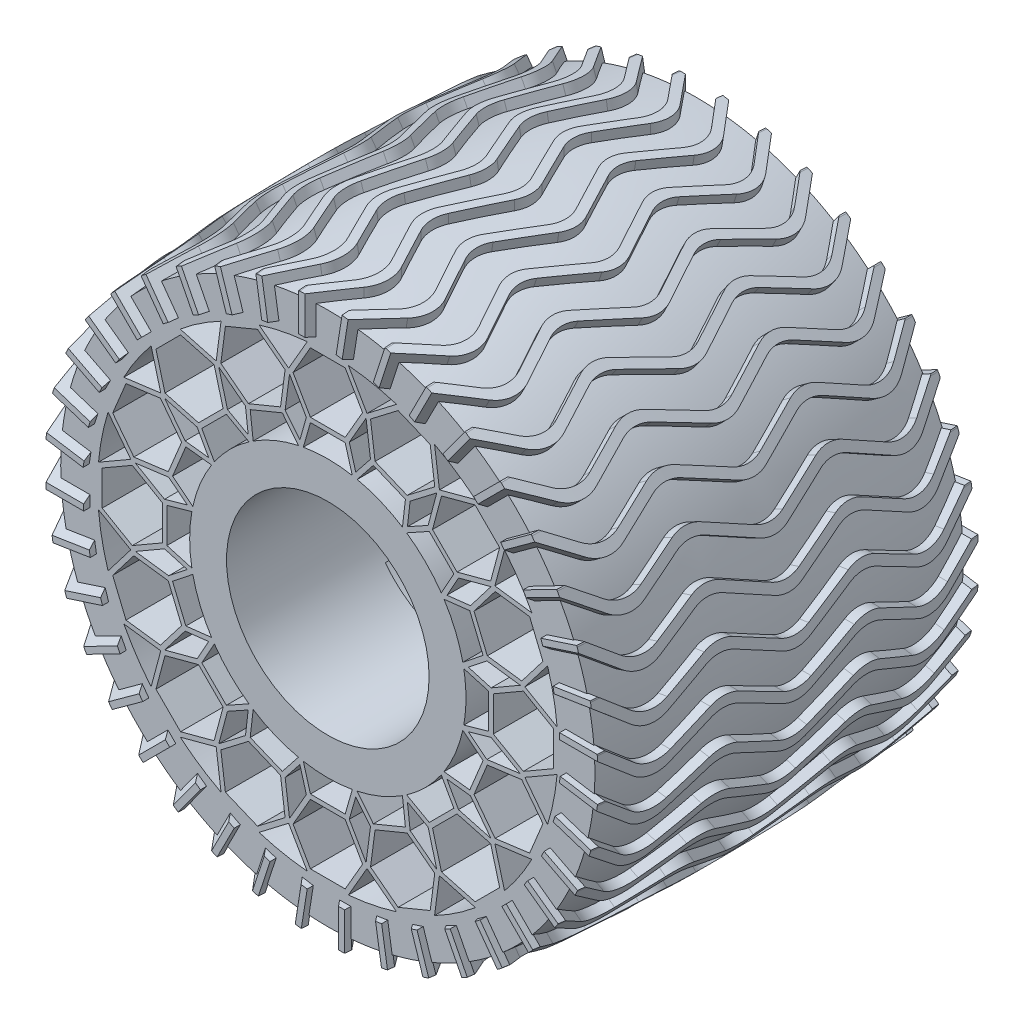
SolidWorks part; units mm, degrees
ref_plane "Alzado" through (0, 0, 0) normal (0, 0, 1) x (1, 0, 0)
ref_plane "Planta" through (0, 0, 0) normal (0, 1, 0) x (1, 0, 0)
ref_plane "Vista lateral" through (0, 0, 0) normal (1, 0, 0) x (0, 0, -1)
sketch "Croquis3" plane through (0, 0, 0) normal (1, 0, 0) x (0, 0, -1)
  line L0 (-55, 0) -> (55, 0) construction
  point P4 (0, 0)
  dimension "D1" = 110
sketch "Croquis2" plane through (0, 0, 0) normal (1, 0, 0) x (0, 0, -1)
  line L0 (0, 0) -> (0, 75) construction
  line L1 (-60, 75) -> (60, 75)
  line L2 (0, 75) -> (0, 87) construction
  line L3 (0, 87) -> (0, 90) construction
  line L4 (-60, 87) -> (60, 87) construction
  line L5 (-60, 87) -> (-60, 75)
  line L6 (60, 87) -> (60, 75)
  line L7 (-60, 33) -> (-15, 33)
  line L8 (60.1117, 33) -> (60.1117, 45)
  line L9 (60.1117, 45) -> (-60, 45)
  line L10 (-60, 45) -> (-60, 33)
  line L11 (-50, 40) -> (50, 40)
  line L14 (15, 33) -> (60.1117, 33)
  line L15 (-15, 33) -> (-15, 35)
  line L16 (-15, 35) -> (-50, 35)
  line L17 (-50, 35) -> (-50, 40)
  line L18 (15, 33) -> (15, 35)
  line L19 (15, 35) -> (50, 35)
  line L20 (50, 35) -> (50, 40)
  arc A0 (60, 87) -> (-60, 87) centre (0, -511.5) ccw
  point P6 (0, 75)
  point P11 (0, 87)
  point P15 (0, 33)
  point P18 (0.0558, 45)
  point P20 (0, 40)
  dimension "D1" = 75
  dimension "D2" = 120
  dimension "D3" = 12
  dimension "D4" = 3
  dimension "D5" = 12
  dimension "D6" = 33
  dimension "D7" = 100
  dimension "D8" = 2
  dimension "D9" = 5
  dimension "D10" = 30
  dimension "D11" = 30
revolve "Revolución1" add sketch "Croquis2" angle 360 about L0
sketch "Croquis4" plane through (0, 0, 0) normal (0, 0, 1) x (1, 0, 0)
  line L0 (-66.7936, 34.7304) -> (-71.7883, 22.6722)
  line L1 (71.7883, 22.6722) -> (66.7936, 34.7304)
  line L2 (57.6475, 48.4185) -> (48.4185, 57.6475)
  line L3 (34.7304, 66.7936) -> (22.6722, 71.7883)
  line L4 (6.5259, 75) -> (-6.5259, 75)
  line L5 (-22.6722, 71.7883) -> (-34.7304, 66.7936)
  line L6 (-48.4185, 57.6475) -> (-57.6475, 48.4185)
  line L7 (-75, 6.5259) -> (-75, -6.5259)
  line L8 (-71.7883, -22.6722) -> (-66.7936, -34.7304)
  line L9 (-57.6475, -48.4185) -> (-48.4185, -57.6475)
  line L10 (-34.7304, -66.7936) -> (-22.6722, -71.7883)
  line L11 (-6.5259, -75) -> (6.5259, -75)
  line L12 (22.6722, -71.7883) -> (34.7304, -66.7936)
  line L13 (48.4185, -57.6475) -> (57.6475, -48.4185)
  line L14 (66.7936, -34.7304) -> (71.7883, -22.6722)
  line L15 (75, -6.5259) -> (75, 6.5259)
  line L16 (0, 0) -> (75, 0) construction
  line L17 (14.9184, 75) -> (-14.9184, -75) construction
  line L18 (-14.9184, 75) -> (14.9184, -75) construction
  line L19 (0, 0) -> (0, 75) construction
  line L20 (-6.5259, 75) -> (-12.7679, 64.1885)
  line L31 (-12.4695, 62.6885) -> (-6.9901, 53.1979)
  line L32 (-6.9901, 53.1979) -> (-9.1077, 45.7875)
  line L33 (-7.9763, 44.2875) -> (-5.6598, 52.3938)
  line L34 (11.3197, 63.6969) -> (5.6598, 73.5)
  line L35 (5.6598, 73.5) -> (-5.6598, 73.5)
  line L36 (-5.6598, 73.5) -> (-11.3197, 63.6969)
  line L37 (-11.3197, 63.6969) -> (-5.6598, 53.8938)
  line L38 (-5.6598, 53.8938) -> (5.6598, 53.8938)
  line L39 (5.6598, 53.8938) -> (11.3197, 63.6969)
  line L40 (-5.6598, 52.3938) -> (5.6598, 52.3938)
  line L41 (5.6598, 52.3938) -> (7.9763, 44.2875)
  line L42 (34.8337, 54.5164) -> (33.3562, 65.7392)
  line L43 (33.3562, 65.7392) -> (22.8982, 70.0711)
  line L44 (22.8982, 70.0711) -> (13.9177, 63.1801)
  line L45 (13.9177, 63.1801) -> (15.3953, 51.9573)
  line L46 (15.3953, 51.9573) -> (25.8533, 47.6254)
  line L47 (6.9901, 53.1979) -> (9.1077, 45.7875)
  line L48 (25.8533, 47.6254) -> (34.8337, 54.5164)
  line L49 (12.4695, 62.6885) -> (6.9901, 53.1979)
  line L50 (6.5259, 75) -> (12.7679, 64.1885)
  line L51 (22.6722, 71.7883) -> (12.7679, 64.1885)
  line L52 (12.4695, 62.6885) -> (13.8999, 51.8234)
  line L53 (9.5789, 43.9687) -> (14.8212, 50.5715)
  line L54 (13.8999, 51.8234) -> (9.1077, 45.7875)
  line L55 (25.2792, 46.2396) -> (24.3172, 37.8639)
  line L56 (26.8159, 46.4734) -> (25.9365, 38.8167)
  line L57 (14.8212, 50.5715) -> (25.2792, 46.2396)
  line L58 (35.5102, 53.1447) -> (26.8159, 46.4734)
  line L59 (34.7304, 66.7936) -> (36.3599, 54.4164)
  line L60 (53.0447, 37.0363) -> (55.9745, 47.9702)
  line L61 (55.9745, 47.9702) -> (47.9702, 55.9745)
  line L62 (47.9702, 55.9745) -> (37.0363, 53.0447)
  line L63 (37.0363, 53.0447) -> (34.1065, 42.1108)
  line L64 (34.1065, 42.1108) -> (42.1108, 34.1065)
  line L65 (42.1108, 34.1065) -> (53.0447, 37.0363)
  line L66 (48.4185, 57.6475) -> (36.3599, 54.4164)
  line L67 (35.5102, 53.1447) -> (32.6738, 42.5593)
  line L68 (25.6759, 36.956) -> (33.0459, 41.0501)
  line L69 (32.6738, 42.5593) -> (25.9365, 38.8167)
  line L70 (41.0501, 33.0459) -> (36.956, 25.6759)
  line L71 (42.5593, 32.6738) -> (38.8167, 25.9365)
  line L72 (33.0459, 41.0501) -> (41.0501, 33.0459)
  line L73 (53.1447, 35.5102) -> (42.5593, 32.6738)
  line L74 (57.6475, 48.4185) -> (54.4164, 36.3599)
  line L75 (63.1801, 13.9177) -> (70.0711, 22.8982)
  line L76 (70.0711, 22.8982) -> (65.7392, 33.3562)
  line L77 (65.7392, 33.3562) -> (54.5164, 34.8337)
  line L78 (54.5164, 34.8337) -> (47.6254, 25.8533)
  line L79 (47.6254, 25.8533) -> (51.9573, 15.3953)
  line L80 (51.9573, 15.3953) -> (63.1801, 13.9177)
  line L81 (66.7936, 34.7304) -> (54.4164, 36.3599)
  line L82 (53.1447, 35.5102) -> (46.4734, 26.8159)
  line L83 (37.8639, 24.3172) -> (46.2396, 25.2792)
  line L84 (46.4734, 26.8159) -> (38.8167, 25.9365)
  line L85 (50.5715, 14.8212) -> (43.9687, 9.5789)
  line L86 (51.8234, 13.8999) -> (45.7875, 9.1077)
  line L87 (46.2396, 25.2792) -> (50.5715, 14.8212)
  line L88 (62.6885, 12.4695) -> (51.8234, 13.8999)
  line L89 (71.7883, 22.6722) -> (64.1885, 12.7679)
  line L90 (63.6969, -11.3197) -> (73.5, -5.6598)
  line L91 (73.5, -5.6598) -> (73.5, 5.6598)
  line L92 (73.5, 5.6598) -> (63.6969, 11.3197)
  line L93 (63.6969, 11.3197) -> (53.8938, 5.6598)
  line L94 (53.8938, 5.6598) -> (53.8938, -5.6598)
  line L95 (53.8938, -5.6598) -> (63.6969, -11.3197)
  line L96 (75, 6.5259) -> (64.1885, 12.7679)
  line L97 (62.6885, 12.4695) -> (53.1979, 6.9901)
  line L98 (44.2875, 7.9763) -> (52.3938, 5.6598)
  line L99 (53.1979, 6.9901) -> (45.7875, 9.1077)
  line L100 (52.3938, -5.6598) -> (44.2875, -7.9763)
  line L101 (53.1979, -6.9901) -> (45.7875, -9.1077)
  line L102 (52.3938, 5.6598) -> (52.3938, -5.6598)
  line L103 (62.6885, -12.4695) -> (53.1979, -6.9901)
  line L104 (75, -6.5259) -> (64.1885, -12.7679)
  line L105 (54.5164, -34.8337) -> (65.7392, -33.3562)
  line L106 (65.7392, -33.3562) -> (70.0711, -22.8982)
  line L107 (70.0711, -22.8982) -> (63.1801, -13.9177)
  line L108 (63.1801, -13.9177) -> (51.9573, -15.3953)
  line L109 (51.9573, -15.3953) -> (47.6254, -25.8533)
  line L110 (47.6254, -25.8533) -> (54.5164, -34.8337)
  line L111 (71.7883, -22.6722) -> (64.1885, -12.7679)
  line L112 (62.6885, -12.4695) -> (51.8234, -13.8999)
  line L113 (43.9687, -9.5789) -> (50.5715, -14.8212)
  line L114 (51.8234, -13.8999) -> (45.7875, -9.1077)
  line L115 (46.2396, -25.2792) -> (37.8639, -24.3172)
  line L116 (46.4734, -26.8159) -> (38.8167, -25.9365)
  line L117 (50.5715, -14.8212) -> (46.2396, -25.2792)
  line L118 (53.1447, -35.5102) -> (46.4734, -26.8159)
  line L119 (66.7936, -34.7304) -> (54.4164, -36.3599)
  line L120 (37.0363, -53.0447) -> (47.9702, -55.9745)
  line L121 (47.9702, -55.9745) -> (55.9745, -47.9702)
  line L122 (55.9745, -47.9702) -> (53.0447, -37.0363)
  line L123 (53.0447, -37.0363) -> (42.1108, -34.1065)
  line L124 (42.1108, -34.1065) -> (34.1065, -42.1108)
  line L125 (34.1065, -42.1108) -> (37.0363, -53.0447)
  line L126 (57.6475, -48.4185) -> (54.4164, -36.3599)
  line L127 (53.1447, -35.5102) -> (42.5593, -32.6738)
  line L128 (36.956, -25.6759) -> (41.0501, -33.0459)
  line L129 (42.5593, -32.6738) -> (38.8167, -25.9365)
  line L130 (33.0459, -41.0501) -> (25.6759, -36.956)
  line L131 (32.6738, -42.5593) -> (25.9365, -38.8167)
  line L132 (41.0501, -33.0459) -> (33.0459, -41.0501)
  line L133 (35.5102, -53.1447) -> (32.6738, -42.5593)
  line L134 (48.4185, -57.6475) -> (36.3599, -54.4164)
  line L135 (13.9177, -63.1801) -> (22.8982, -70.0711)
  line L136 (22.8982, -70.0711) -> (33.3562, -65.7392)
  line L137 (33.3562, -65.7392) -> (34.8337, -54.5164)
  line L138 (34.8337, -54.5164) -> (25.8533, -47.6254)
  line L139 (25.8533, -47.6254) -> (15.3953, -51.9573)
  line L140 (15.3953, -51.9573) -> (13.9177, -63.1801)
  line L141 (34.7304, -66.7936) -> (36.3599, -54.4164)
  line L142 (35.5102, -53.1447) -> (26.8159, -46.4734)
  line L143 (24.3172, -37.8639) -> (25.2792, -46.2396)
  line L144 (26.8159, -46.4734) -> (25.9365, -38.8167)
  line L145 (14.8212, -50.5715) -> (9.5789, -43.9687)
  line L146 (13.8999, -51.8234) -> (9.1077, -45.7875)
  line L147 (25.2792, -46.2396) -> (14.8212, -50.5715)
  line L148 (12.4695, -62.6885) -> (13.8999, -51.8234)
  line L149 (22.6722, -71.7883) -> (12.7679, -64.1885)
  line L150 (-11.3197, -63.6969) -> (-5.6598, -73.5)
  line L151 (-5.6598, -73.5) -> (5.6598, -73.5)
  line L152 (5.6598, -73.5) -> (11.3197, -63.6969)
  line L153 (11.3197, -63.6969) -> (5.6598, -53.8938)
  line L154 (5.6598, -53.8938) -> (-5.6598, -53.8938)
  line L155 (-5.6598, -53.8938) -> (-11.3197, -63.6969)
  line L156 (6.5259, -75) -> (12.7679, -64.1885)
  line L157 (12.4695, -62.6885) -> (6.9901, -53.1979)
  line L158 (7.9763, -44.2875) -> (5.6598, -52.3938)
  line L159 (6.9901, -53.1979) -> (9.1077, -45.7875)
  line L160 (-5.6598, -52.3938) -> (-7.9763, -44.2875)
  line L161 (-6.9901, -53.1979) -> (-9.1077, -45.7875)
  line L162 (5.6598, -52.3938) -> (-5.6598, -52.3938)
  line L163 (-12.4695, -62.6885) -> (-6.9901, -53.1979)
  line L164 (-6.5259, -75) -> (-12.7679, -64.1885)
  line L165 (-34.8337, -54.5164) -> (-33.3562, -65.7392)
  line L166 (-33.3562, -65.7392) -> (-22.8982, -70.0711)
  line L167 (-22.8982, -70.0711) -> (-13.9177, -63.1801)
  line L168 (-13.9177, -63.1801) -> (-15.3953, -51.9573)
  line L169 (-15.3953, -51.9573) -> (-25.8533, -47.6254)
  line L170 (-25.8533, -47.6254) -> (-34.8337, -54.5164)
  line L171 (-22.6722, -71.7883) -> (-12.7679, -64.1885)
  line L172 (-12.4695, -62.6885) -> (-13.8999, -51.8234)
  line L173 (-9.5789, -43.9687) -> (-14.8212, -50.5715)
  line L174 (-13.8999, -51.8234) -> (-9.1077, -45.7875)
  line L175 (-25.2792, -46.2396) -> (-24.3172, -37.8639)
  line L176 (-26.8159, -46.4734) -> (-25.9365, -38.8167)
  line L177 (-14.8212, -50.5715) -> (-25.2792, -46.2396)
  line L178 (-35.5102, -53.1447) -> (-26.8159, -46.4734)
  line L179 (-34.7304, -66.7936) -> (-36.3599, -54.4164)
  line L180 (-53.0447, -37.0363) -> (-55.9745, -47.9702)
  line L181 (-55.9745, -47.9702) -> (-47.9702, -55.9745)
  line L182 (-47.9702, -55.9745) -> (-37.0363, -53.0447)
  line L183 (-37.0363, -53.0447) -> (-34.1065, -42.1108)
  line L184 (-34.1065, -42.1108) -> (-42.1108, -34.1065)
  line L185 (-42.1108, -34.1065) -> (-53.0447, -37.0363)
  line L186 (-48.4185, -57.6475) -> (-36.3599, -54.4164)
  line L187 (-35.5102, -53.1447) -> (-32.6738, -42.5593)
  line L188 (-25.6759, -36.956) -> (-33.0459, -41.0501)
  line L189 (-32.6738, -42.5593) -> (-25.9365, -38.8167)
  line L190 (-41.0501, -33.0459) -> (-36.956, -25.6759)
  line L191 (-42.5593, -32.6738) -> (-38.8167, -25.9365)
  line L192 (-33.0459, -41.0501) -> (-41.0501, -33.0459)
  line L193 (-53.1447, -35.5102) -> (-42.5593, -32.6738)
  line L194 (-57.6475, -48.4185) -> (-54.4164, -36.3599)
  line L195 (-63.1801, -13.9177) -> (-70.0711, -22.8982)
  line L196 (-70.0711, -22.8982) -> (-65.7392, -33.3562)
  line L197 (-65.7392, -33.3562) -> (-54.5164, -34.8337)
  line L198 (-54.5164, -34.8337) -> (-47.6254, -25.8533)
  line L199 (-47.6254, -25.8533) -> (-51.9573, -15.3953)
  line L200 (-51.9573, -15.3953) -> (-63.1801, -13.9177)
  line L201 (-66.7936, -34.7304) -> (-54.4164, -36.3599)
  line L202 (-53.1447, -35.5102) -> (-46.4734, -26.8159)
  line L203 (-37.8639, -24.3172) -> (-46.2396, -25.2792)
  line L204 (-46.4734, -26.8159) -> (-38.8167, -25.9365)
  line L205 (-50.5715, -14.8212) -> (-43.9687, -9.5789)
  line L206 (-51.8234, -13.8999) -> (-45.7875, -9.1077)
  line L207 (-46.2396, -25.2792) -> (-50.5715, -14.8212)
  line L208 (-62.6885, -12.4695) -> (-51.8234, -13.8999)
  line L209 (-71.7883, -22.6722) -> (-64.1885, -12.7679)
  line L210 (-63.6969, 11.3197) -> (-73.5, 5.6598)
  line L211 (-73.5, 5.6598) -> (-73.5, -5.6598)
  line L212 (-73.5, -5.6598) -> (-63.6969, -11.3197)
  line L213 (-63.6969, -11.3197) -> (-53.8938, -5.6598)
  line L214 (-53.8938, -5.6598) -> (-53.8938, 5.6598)
  line L215 (-53.8938, 5.6598) -> (-63.6969, 11.3197)
  line L216 (-75, -6.5259) -> (-64.1885, -12.7679)
  line L217 (-62.6885, -12.4695) -> (-53.1979, -6.9901)
  line L218 (-44.2875, -7.9763) -> (-52.3938, -5.6598)
  line L219 (-53.1979, -6.9901) -> (-45.7875, -9.1077)
  line L220 (-52.3938, 5.6598) -> (-44.2875, 7.9763)
  line L221 (-53.1979, 6.9901) -> (-45.7875, 9.1077)
  line L222 (-52.3938, -5.6598) -> (-52.3938, 5.6598)
  line L223 (-62.6885, 12.4695) -> (-53.1979, 6.9901)
  line L224 (-75, 6.5259) -> (-64.1885, 12.7679)
  line L225 (-54.5164, 34.8337) -> (-65.7392, 33.3562)
  line L226 (-65.7392, 33.3562) -> (-70.0711, 22.8982)
  line L227 (-70.0711, 22.8982) -> (-63.1801, 13.9177)
  line L228 (-63.1801, 13.9177) -> (-51.9573, 15.3953)
  line L229 (-51.9573, 15.3953) -> (-47.6254, 25.8533)
  line L230 (-47.6254, 25.8533) -> (-54.5164, 34.8337)
  line L231 (-71.7883, 22.6722) -> (-64.1885, 12.7679)
  line L232 (-62.6885, 12.4695) -> (-51.8234, 13.8999)
  line L233 (-43.9687, 9.5789) -> (-50.5715, 14.8212)
  line L234 (-51.8234, 13.8999) -> (-45.7875, 9.1077)
  line L235 (-46.2396, 25.2792) -> (-37.8639, 24.3172)
  line L236 (-46.4734, 26.8159) -> (-38.8167, 25.9365)
  line L237 (-50.5715, 14.8212) -> (-46.2396, 25.2792)
  line L238 (-53.1447, 35.5102) -> (-46.4734, 26.8159)
  line L239 (-66.7936, 34.7304) -> (-54.4164, 36.3599)
  line L240 (-37.0363, 53.0447) -> (-47.9702, 55.9745)
  line L241 (-47.9702, 55.9745) -> (-55.9745, 47.9702)
  line L242 (-55.9745, 47.9702) -> (-53.0447, 37.0363)
  line L243 (-53.0447, 37.0363) -> (-42.1108, 34.1065)
  line L244 (-42.1108, 34.1065) -> (-34.1065, 42.1108)
  line L245 (-34.1065, 42.1108) -> (-37.0363, 53.0447)
  line L246 (-57.6475, 48.4185) -> (-54.4164, 36.3599)
  line L247 (-53.1447, 35.5102) -> (-42.5593, 32.6738)
  line L248 (-36.956, 25.6759) -> (-41.0501, 33.0459)
  line L249 (-42.5593, 32.6738) -> (-38.8167, 25.9365)
  line L250 (-33.0459, 41.0501) -> (-25.6759, 36.956)
  line L251 (-32.6738, 42.5593) -> (-25.9365, 38.8167)
  line L252 (-41.0501, 33.0459) -> (-33.0459, 41.0501)
  line L253 (-35.5102, 53.1447) -> (-32.6738, 42.5593)
  line L254 (-48.4185, 57.6475) -> (-36.3599, 54.4164)
  line L255 (-13.9177, 63.1801) -> (-22.8982, 70.0711)
  line L256 (-22.8982, 70.0711) -> (-33.3562, 65.7392)
  line L257 (-33.3562, 65.7392) -> (-34.8337, 54.5164)
  line L258 (-34.8337, 54.5164) -> (-25.8533, 47.6254)
  line L259 (-25.8533, 47.6254) -> (-15.3953, 51.9573)
  line L260 (-15.3953, 51.9573) -> (-13.9177, 63.1801)
  line L261 (-34.7304, 66.7936) -> (-36.3599, 54.4164)
  line L262 (-35.5102, 53.1447) -> (-26.8159, 46.4734)
  line L263 (-24.3172, 37.8639) -> (-25.2792, 46.2396)
  line L264 (-26.8159, 46.4734) -> (-25.9365, 38.8167)
  line L265 (-14.8212, 50.5715) -> (-9.5789, 43.9687)
  line L266 (-13.8999, 51.8234) -> (-9.1077, 45.7875)
  line L267 (-25.2792, 46.2396) -> (-14.8212, 50.5715)
  line L268 (-12.4695, 62.6885) -> (-13.8999, 51.8234)
  line L269 (-22.6722, 71.7883) -> (-12.7679, 64.1885)
  arc A0 (-22.3975, 71.5776) -> (-34.7755, 66.4504) centre (0, 0) ccw construction
  circle A1 centre (0, 0) radius 75 construction
  arc A3 (-7.9763, 44.2875) -> (-8.7791, 44.1353) centre (0, 0) ccw
  circle A5 centre (0, 63.6969) radius 9.8031 construction
  circle A9 centre (0, 0) radius 45 construction
  arc A10 (8.7791, 44.1353) -> (7.9763, 44.2875) centre (0, 0) ccw
  arc A11 (9.5789, 43.9687) -> (8.7791, 44.1353) centre (0, 0) ccw
  arc A12 (25.0007, 37.4161) -> (24.3172, 37.8639) centre (0, 0) ccw
  arc A13 (25.6759, 36.956) -> (25.0007, 37.4161) centre (0, 0) ccw
  arc A14 (37.4161, 25.0007) -> (36.956, 25.6759) centre (0, 0) ccw
  arc A15 (37.8639, 24.3172) -> (37.4161, 25.0007) centre (0, 0) ccw
  arc A16 (44.1353, 8.7791) -> (43.9687, 9.5789) centre (0, 0) ccw
  arc A17 (44.2875, 7.9763) -> (44.1353, 8.7791) centre (0, 0) ccw
  arc A18 (44.1353, -8.7791) -> (44.2875, -7.9763) centre (0, 0) ccw
  arc A19 (43.9687, -9.5789) -> (44.1353, -8.7791) centre (0, 0) ccw
  arc A20 (37.4161, -25.0007) -> (37.8639, -24.3172) centre (0, 0) ccw
  arc A21 (36.956, -25.6759) -> (37.4161, -25.0007) centre (0, 0) ccw
  arc A22 (25.0007, -37.4161) -> (25.6759, -36.956) centre (0, 0) ccw
  arc A23 (24.3172, -37.8639) -> (25.0007, -37.4161) centre (0, 0) ccw
  arc A24 (8.7791, -44.1353) -> (9.5789, -43.9687) centre (0, 0) ccw
  arc A25 (7.9763, -44.2875) -> (8.7791, -44.1353) centre (0, 0) ccw
  arc A26 (-8.7791, -44.1353) -> (-7.9763, -44.2875) centre (0, 0) ccw
  arc A27 (-9.5789, -43.9687) -> (-8.7791, -44.1353) centre (0, 0) ccw
  arc A28 (-25.0007, -37.4161) -> (-24.3172, -37.8639) centre (0, 0) ccw
  arc A29 (-25.6759, -36.956) -> (-25.0007, -37.4161) centre (0, 0) ccw
  arc A30 (-37.4161, -25.0007) -> (-36.956, -25.6759) centre (0, 0) ccw
  arc A31 (-37.8639, -24.3172) -> (-37.4161, -25.0007) centre (0, 0) ccw
  arc A32 (-44.1353, -8.7791) -> (-43.9687, -9.5789) centre (0, 0) ccw
  arc A33 (-44.2875, -7.9763) -> (-44.1353, -8.7791) centre (0, 0) ccw
  arc A34 (-44.1353, 8.7791) -> (-44.2875, 7.9763) centre (0, 0) ccw
  arc A35 (-43.9687, 9.5789) -> (-44.1353, 8.7791) centre (0, 0) ccw
  arc A36 (-37.4161, 25.0007) -> (-37.8639, 24.3172) centre (0, 0) ccw
  arc A37 (-36.956, 25.6759) -> (-37.4161, 25.0007) centre (0, 0) ccw
  arc A38 (-25.0007, 37.4161) -> (-25.6759, 36.956) centre (0, 0) ccw
  arc A39 (-24.3172, 37.8639) -> (-25.0007, 37.4161) centre (0, 0) ccw
  arc A40 (-8.7791, 44.1353) -> (-9.5789, 43.9687) centre (0, 0) ccw
  arc A41 (6.6989, 74.7002) -> (-6.6989, 74.7002) centre (0, 0) ccw construction
  arc A42 (34.7755, 66.4504) -> (22.3975, 71.5776) centre (0, 0) ccw construction
  arc A43 (57.5579, 48.0842) -> (48.0842, 57.5579) centre (0, 0) ccw construction
  arc A44 (71.5776, 22.3975) -> (66.4504, 34.7755) centre (0, 0) ccw construction
  arc A45 (74.7002, -6.6989) -> (74.7002, 6.6989) centre (0, 0) ccw construction
  arc A46 (66.4504, -34.7755) -> (71.5776, -22.3975) centre (0, 0) ccw construction
  arc A47 (48.0842, -57.5579) -> (57.5579, -48.0842) centre (0, 0) ccw construction
  arc A48 (22.3975, -71.5776) -> (34.7755, -66.4504) centre (0, 0) ccw construction
  arc A49 (-6.6989, -74.7002) -> (6.6989, -74.7002) centre (0, 0) ccw construction
  arc A50 (-34.7755, -66.4504) -> (-22.3975, -71.5776) centre (0, 0) ccw construction
  arc A51 (-57.5579, -48.0842) -> (-48.0842, -57.5579) centre (0, 0) ccw construction
  arc A52 (-71.5776, -22.3975) -> (-66.4504, -34.7755) centre (0, 0) ccw construction
  arc A53 (-74.7002, 6.6989) -> (-74.7002, -6.6989) centre (0, 0) ccw construction
  arc A54 (-66.4504, 34.7755) -> (-71.5776, 22.3975) centre (0, 0) ccw construction
  arc A55 (-48.0842, 57.5579) -> (-57.5579, 48.0842) centre (0, 0) ccw construction
  point P1 (75, 0)
  point P38 (0, 52.383)
  point P385 (0, 0)
  dimension "D7" = 1.5
  dimension "D1" = 1.5
  dimension "D2" = 1.5
  dimension "D3" = 1.5
  dimension "D4" = 1.5
  dimension "D5" = 1.5
  dimension "D6" = 1.5
  dimension "D8" = 1.5
  dimension "D9" = 16
extrude "Saliente-Extruir1" add sketch "Croquis4" along normal mid plane 120
sketch "Croquis5" plane through (0, 0, 0) normal (0, 0, 1) x (1, 0, 0)
  line L0 (0, 0) -> (0, 40) construction
  line L1 (4.1364, 32.7397) -> (5.4737, 43.3242)
  line L2 (-4.1364, 32.7397) -> (-5.4737, 43.3242)
  line L3 (30.4216, -12.7876) -> (40.2567, -16.9218)
  line L4 (26.2852, -19.9521) -> (34.783, -26.4024)
  line L5 (-26.2852, -19.9521) -> (-34.783, -26.4024)
  line L6 (-30.4216, -12.7876) -> (-40.2567, -16.9218)
  arc A0 (4.1364, 32.7397) -> (-4.1364, 32.7397) centre (0, 0) ccw
  arc A1 (5.4737, 43.3242) -> (-5.4737, 43.3242) centre (0, 0) ccw
  arc A2 (-30.4216, -12.7876) -> (-26.2852, -19.9521) centre (0, 0) ccw
  arc A3 (-40.2567, -16.9218) -> (-34.783, -26.4024) centre (0, 0) ccw
  arc A4 (26.2852, -19.9521) -> (30.4216, -12.7876) centre (0, 0) ccw
  arc A5 (34.783, -26.4024) -> (40.2567, -16.9218) centre (0, 0) ccw
  circle A6 centre (0, 0) radius 33 construction
  point P14 (0, 0)
  dimension "D1" = 40
  dimension "D3" = 3
extrude "Saliente-Extruir2" add sketch "Croquis5" along normal mid plane 120
ref_plane "Plano1" through (0, 90, 0) normal (0, 1, 0) x (1, 0, 0)
sketch "Croquis6" plane through (0, 90, 0) normal (0, 1, 0) x (1, 0, 0)
  line L0 (0, -62) -> (0, 62) construction
  line L5 (0, 62) -> (7.5, 62) construction
  line L6 (7.5, 62) -> (7.5, -62) construction
  line L7 (7.5, -62) -> (0, -62) construction
  line L8 (0, -62) -> (-7.5, -62) construction
  line L9 (-7.5, -62) -> (-7.5, 62) construction
  line L10 (-7.5, 62) -> (0, 62) construction
  line L11 (5.2629, 4.4731) -> (-1.8989, 18.7928)
  line L12 (-1.887, 27.7627) -> (4.5493, 40.5468)
  line L13 (3.2981, 51.4474) -> (-5.5, 62)
  line L14 (-5.5, 62) -> (-7.5, 62)
  line L15 (-7.5, 62) -> (-7.5, 59.714)
  line L16 (-7.5, 59.714) -> (-0.2666, 51.0382)
  line L17 (0.9846, 40.1377) -> (-5.2435, 27.7672)
  line L18 (-5.2554, 18.7972) -> (1.9086, 4.4731)
  line L19 (0, 0) -> (-11.8513, 0) construction
  line L20 (5.2629, -4.4731) -> (-1.8989, -18.7928)
  line L21 (-5.2554, -18.7972) -> (1.9086, -4.4731)
  line L22 (0.9846, -40.1377) -> (-5.2435, -27.7672)
  line L23 (-1.887, -27.7627) -> (4.5493, -40.5468)
  line L24 (-7.5, -59.714) -> (-0.2666, -51.0382)
  line L25 (3.2981, -51.4474) -> (-5.5, -62)
  line L26 (-7.5, -62) -> (-7.5, -59.714)
  line L27 (-5.5, -62) -> (-7.5, -62)
  arc A0 (0.9846, -40.1377) -> (-0.2666, -51.0382) centre (-7.9473, -44.6345) cw
  arc A1 (4.5493, -40.5468) -> (3.2981, -51.4474) centre (-4.3825, -45.0437) cw
  arc A2 (-1.8989, -18.7928) -> (-1.887, -27.7627) centre (7.0449, -23.2659) ccw
  arc A3 (-5.2554, -18.7972) -> (-5.2435, -27.7672) centre (3.6884, -23.2703) ccw
  arc A4 (1.9086, -4.4731) -> (1.9086, 4.4731) centre (-7.0352, 0) ccw
  arc A5 (5.2629, 4.4731) -> (5.2629, -4.4731) centre (-3.6809, 0) cw
  arc A6 (-1.8989, 18.7928) -> (-1.887, 27.7627) centre (7.0449, 23.2659) cw
  arc A7 (-5.2435, 27.7672) -> (-5.2554, 18.7972) centre (3.6884, 23.2703) ccw
  arc A8 (-0.2666, 51.0382) -> (0.9846, 40.1377) centre (-7.9473, 44.6345) cw
  arc A9 (4.5493, 40.5468) -> (3.2981, 51.4474) centre (-4.3825, 45.0437) ccw
  point P4 (0, 0)
  point P28 (3.9352, -45.9984)
  point P31 (7.5, -46.4076)
  point P34 (-4.1435, -23.2807)
  point P37 (-7.5, -23.2852)
  point P41 (7.5, 0)
  point P44 (-4.1435, 23.2807)
  point P47 (-7.5, 23.2852)
  point P50 (3.9352, 45.9984)
  point P53 (7.5, 46.4076)
  dimension "D8" = 10
  dimension "D1" = 124
  dimension "D2" = 15
  dimension "D3" = 7.5
  dimension "D4" = 2
  dimension "D5" = 3
  dimension "D6" = 3
  dimension "D7" = 3
extrude "Saliente-Extruir3" add sketch "Croquis6" along normal mid plane 25
sketch "Croquis7" plane through (0, 0, 0) normal (1, 0, 0) x (0, 0, -1)
  line L0 (0, 0) -> (0, 90) construction
  line L1 (0, 90) -> (0, 93) construction
  line L2 (-60, 87) -> (-60, 90) construction
  line L3 (60, 87) -> (60, 90) construction
  line L4 (-66.2544, 89.3399) -> (-66.2544, 110.0646)
  line L5 (-66.2544, 110.0646) -> (69.8702, 110.0646)
  line L6 (69.8702, 110.0646) -> (69.8702, 88.9282)
  arc A0 (69.8702, 88.9282) -> (-66.2544, 89.3399) centre (0, -508.5) ccw
  dimension "D1" = 90
  dimension "D2" = 3
  dimension "D3" = 3
extrude "Cortar-Extruir1" cut sketch "Croquis7" against normal mid plane 25
pattern_circular "MatrizC1" count 40 over 360 about axis through (0, 0, 55) along (0, 0, -1) of "Saliente-Extruir3", "Cortar-Extruir1"
